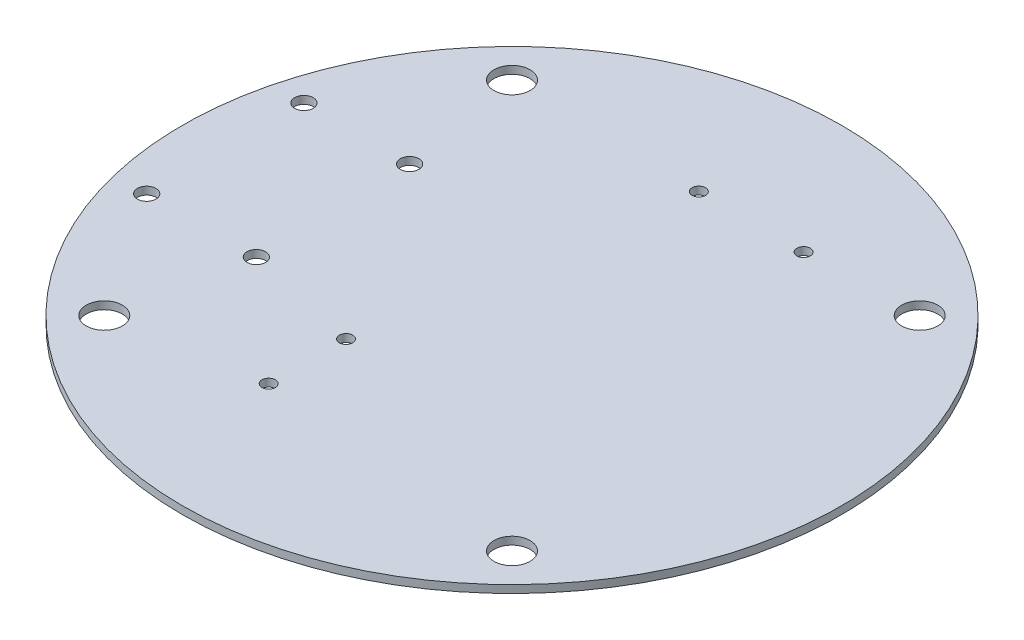
SolidWorks part; units mm, degrees
ref_plane "Front Plane" through (0, 0, 0) normal (0, 0, 1) x (1, 0, 0)
ref_plane "Top Plane" through (0, 0, 0) normal (0, 1, 0) x (1, 0, 0)
ref_plane "Right Plane" through (0, 0, 0) normal (1, 0, 0) x (0, 0, -1)
sketch "Sketch1" plane through (0, 0, 0) normal (0, 1, 0) x (1, 0, 0)
  circle A0 centre (0, 0) radius 63.9
  dimension "PCBdiam" = 127.8
extrude "Boss-Extrude1" add sketch "Sketch1" along normal blind 1.5
hole_wizard "M6 Clearance Hole1" positions "Sketch2" profile "Sketch4" hole size "M6" standard "ANSI Metric" end condition through all
sketch "Sketch2" plane through (0, 1.5, 0) normal (0, 1, 0) x (1, 0, 0)
  line L0 (0, 0) -> (-28.5457, 28.5457) construction
  line L1 (-39.5273, -39.5273) -> (0, 0) construction
  line L3 (0, 0) -> (-73.422, 0) construction
  circle A0 centre (0, 0) radius 63.9 construction
  ellipse E2 centre (-116.4291, -176.9435) end of major axis (-117.7556, -176.0714) minor radius 1.3748
  ellipse E3 centre (-116.4291, -176.9435) end of major axis (-115.1026, -177.8157) minor radius 1.3748
  point P7 (-39.5273, -39.5273)
  point P82 (-34.9144, 34.9144)
  point P83 (-73.422, 0.2717)
  point P84 (-23.0973, -55.9572)
  point P85 (-55.7307, -23.3239)
  point P86 (0, 0)
  point P87 (0, 0)
  dimension "D1" = 0
  dimension "holeRadius" = 55.9
  dimension "D2" = 45
sketch "Sketch4" plane through (-39.5273, 1.5, 39.5273) normal (1, 0, 0) x (0, 0, 1)
  line L0 (0, 0) -> (0, 1.5)
  line L1 (0, 1.5) -> (3.5, 1.5)
  line L2 (3.5, 1.5) -> (3.5, 0)
  line L5 (3.5, 0) -> (0, 0)
  line L11 (0, -6.35) -> (0, 107.95) construction
  dimension "Thru Hole Dia." = 7
  dimension "Thru Hole Depth" = 1.5
pattern_circular "CirPattern1" count 4 over 360 about axis through (0, 1.5, 0) along (0, -1, 0) of "M6 Clearance Hole1"
sketch "Teensy Outline" plane through (0, 1.5, 0) normal (0, 1, 0) x (1, 0, 0)
  line L1 (-29.654, 48.9) -> (-12, 48.9)
  line L2 (-29.654, 48.9) -> (-29.654, -9.52)
  line L3 (-29.654, -9.52) -> (-12, -9.52)
  line L4 (-12, 48.9) -> (-12, -9.52)
  circle A1 centre (0, 0) radius 63.9 construction
  dimension "D1" = 17.654
  dimension "D2" = 58.42
  dimension "D3" = 12
  dimension "D4" = 15
sketch "BMP390 Outline" plane through (0, 1.5, 0) normal (0, 1, 0) x (1, 0, 0)
  line L0 (17.61, 52.9) -> (-5.25, 52.9) construction
  line L2 (20.15, 54.24) -> (-5.25, 54.24)
  line L3 (-5.25, 54.24) -> (-5.25, 36.46)
  line L4 (20.15, 36.46) -> (-5.25, 36.46)
  line L6 (20.15, 54.24) -> (20.15, 36.46)
  line L7 (17.61, 52.9) -> (17.61, 36.46) construction
  line L8 (-29.654, 48.9) -> (-12, 48.9) construction
  line L9 (-12, 48.9) -> (-12, -9.52) construction
  dimension "D1" = 17.78
  dimension "D2" = 25.4
  dimension "D3" = 1.34
  dimension "D4" = 4
  dimension "D5" = 6.75
  dimension "D6" = 5.08
sketch "NEO-6M Outline" plane through (0, 1.5, 0) normal (0, 1, 0) x (1, 0, 0)
  line L0 (-50.84, 17.78) -> (-50.84, 15.24) construction
  line L1 (-58.34, 17.78) -> (-32, 17.78)
  line L2 (-58.34, 17.78) -> (-58.34, -17.78)
  line L3 (-58.34, -17.78) -> (-32, -17.78)
  line L4 (-32, 17.78) -> (-32, -17.78)
  line L5 (-50.84, 15.24) -> (-39.5, 15.24) construction
  line L6 (-39.5, 15.24) -> (-39.5, 17.78) construction
  point P4 (-32, 0)
  point P9 (-45.17, 15.24)
  point P11 (-45.17, 17.78)
  dimension "D1" = 26.34
  dimension "D2" = 35.56
  dimension "D3" = 32
  dimension "D4" = 7.5
  dimension "D5" = 2.54
sketch "Xbee outline" plane through (0, 1.5, 0) normal (0, 1, 0) x (1, 0, 0)
  line L0 (9, 6.5) -> (26, 6.5) construction
  line L1 (26, 1.875) -> (26, 11.125)
  line L2 (26, 11.125) -> (19.5, 18.75)
  line L3 (19.5, 18.75) -> (-7, 18.75)
  line L4 (-7, 18.75) -> (-7, -5.75)
  line L5 (19.5, -5.75) -> (-7, -5.75)
  line L6 (26, 1.875) -> (19.5, -5.75)
  line L7 (0, 0) -> (72.9219, 0) construction
  line L9 (-12, 48.9) -> (-12, -9.52) construction
  line L10 (61, 12) -> (26, 12) construction
  line L11 (61, 12) -> (61, 1) construction
  line L12 (61, 1) -> (26, 1) construction
  line L13 (26, 12) -> (26, 1) construction
  point P7 (-7, 6.5)
  point P11 (26, 6.5)
  dimension "D1" = 24.5
  dimension "D2" = 33
  dimension "D3" = 26.5
  dimension "D4" = 9.25
  dimension "D5" = 16
  dimension "D6" = 35
  dimension "D7" = 11
  dimension "D8" = 6.5
  dimension "D9" = 5
sketch "Accel, gyro outline" plane through (0, 1.5, 0) normal (0, 1, 0) x (1, 0, 0)
  line L0 (47.32, 31.44) -> (27, 31.44) construction
  line L1 (52.4, 32.78) -> (27, 32.78)
  line L2 (27, 32.78) -> (27, 15)
  line L3 (52.4, 15) -> (27, 15)
  line L4 (52.4, 32.78) -> (52.4, 15)
  line L5 (47.32, 31.44) -> (47.32, 16.34) construction
  line L6 (27, 23.89) -> (52.4, 23.89) construction
  line L7 (47.32, 16.34) -> (27, 16.34) construction
  dimension "D1" = 17.78
  dimension "D2" = 25.4
  dimension "D3" = 1.34
  dimension "D4" = 5.08
  dimension "D5" = 15
  dimension "D6" = 27
sketch "Sketch17" plane through (0, 1.5, 0) normal (0, 1, 0) x (1, 0, 0)
  line L0 (-29.654, -23.5273) -> (-36.154, -23.5273) construction
  line L1 (-29.654, -17.5273) -> (-9.654, -17.5273)
  line L2 (-29.654, -17.5273) -> (-29.654, -37.5273)
  line L3 (-29.654, -37.5273) -> (-9.654, -37.5273)
  line L4 (-9.654, -17.5273) -> (-9.654, -37.5273)
  line L5 (-36.154, -23.5273) -> (-36.154, -31.5273) construction
  line L6 (-36.154, -31.5273) -> (-29.654, -31.5273) construction
  line L7 (-29.654, 48.9) -> (-29.654, -9.52) construction
  circle A0 centre (-39.5273, -39.5273) radius 3.5 construction
  point P8 (-36.154, -27.5273)
  point P9 (-29.654, -27.5273)
  dimension "D1" = 20
  dimension "D2" = 20
  dimension "D3" = 6.5
  dimension "D4" = 8
  dimension "D5" = 0
  dimension "D6" = 2
hole_wizard "M2 Clearance Hole1" positions "Sketch20" profile "Sketch19" hole size "M2" standard "ANSI Metric" end condition through all
sketch "Sketch20" plane through (0, 1.5, 0) normal (0, 1, 0) x (1, 0, 0)
  circle A0 centre (-2.71, 38.93) radius 1.2493 construction
  circle A1 centre (17.61, 38.93) radius 1.2493 construction
  circle A2 centre (-12.154, -20.0273) radius 1.25 construction
  circle A3 centre (-12.154, -20.0273) radius 1.25 construction
  circle A4 centre (-12.154, -35.0273) radius 1.25 construction
  circle A5 centre (-12.154, -35.0273) radius 1.25 construction
  point P1 (-2.71, 38.93)
  point P7 (17.61, 38.93)
  point P13 (-12.154, -20.0273)
  point P16 (-12.154, -35.0273)
sketch "Sketch19" plane through (-2.71, 1.5, -38.93) normal (1, 0, 0) x (0, 0, 1)
  line L0 (0, 0) -> (0, 1.5)
  line L1 (0, 1.5) -> (1.3, 1.5)
  line L2 (1.3, 1.5) -> (1.3, 0)
  line L5 (1.3, 0) -> (0, 0)
  line L11 (0, -6.35) -> (0, 107.95) construction
  dimension "Thru Hole Dia." = 2.6
  dimension "Thru Hole Depth" = 1.5
hole_wizard "M3 Clearance Hole2" positions "Sketch21" profile "Sketch22" hole size "M3" standard "ANSI Metric" end condition through all
sketch "Sketch21" plane through (0, 1.5, 0) normal (0, 1, 0) x (1, 0, 0)
  point P0 (-55.8645, 15.5117)
  point P3 (-55.8645, -14.9683)
  point P6 (-34.6045, -14.9683)
  point P9 (-35.3665, 15.5117)
sketch "Sketch22" plane through (-55.8645, 1.5, -15.5117) normal (1, 0, 0) x (0, 0, 1)
  line L0 (0, 0) -> (0, 1.5)
  line L1 (0, 1.5) -> (1.8, 1.5)
  line L2 (1.8, 1.5) -> (1.8, 0)
  line L5 (1.8, 0) -> (0, 0)
  line L11 (0, -6.35) -> (0, 107.95) construction
  dimension "Thru Hole Dia." = 3.6
  dimension "Thru Hole Depth" = 1.5
